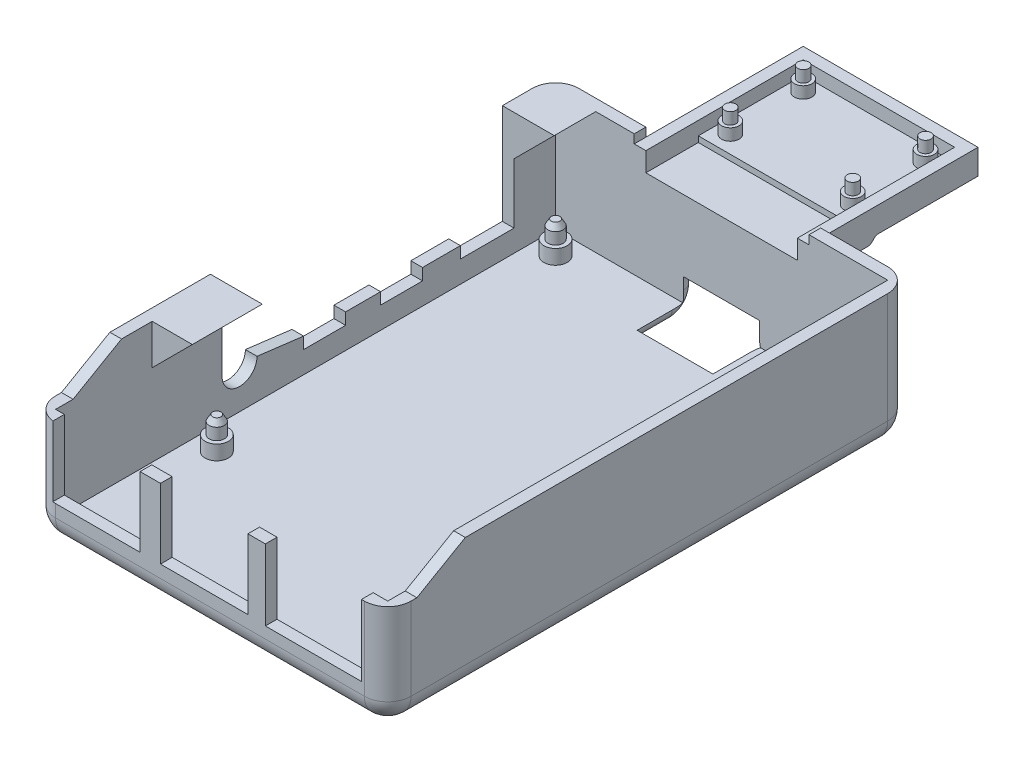
SolidWorks part; units mm, degrees
ref_plane "Płaszczyzna przednia" through (0, 0, 0) normal (0, 0, 1) x (1, 0, 0)
ref_plane "Płaszczyzna górna" through (0, 0, 0) normal (0, 1, 0) x (1, 0, 0)
ref_plane "Płaszczyzna prawa" through (0, 0, 0) normal (1, 0, 0) x (0, 0, -1)
sketch "Szkic1" plane through (0, 0, 0) normal (0, 1, 0) x (1, 0, 0)
  line L1 (-30.5, 44.9) -> (30.5, 44.9)
  line L2 (-30.5, 44.9) -> (-30.5, -44.9)
  line L3 (-30.5, -44.9) -> (30.5, -44.9)
  line L4 (30.5, 44.9) -> (30.5, -44.9)
  line L5 (-30.5, 44.9) -> (30.5, -44.9) construction
  line L6 (-30.5, -44.9) -> (30.5, 44.9) construction
  point P0 (0, 0)
  dimension "D1" = 61
  dimension "D2" = 89.8
extrude "Dodanie-wyciągnięcie1" add sketch "Szkic1" along normal blind 2
sketch "Szkic2" plane through (0, 2, 0) normal (0, 1, 0) x (1, 0, 0)
  line L0 (28.5, -42.9) -> (28.5, 42.9)
  line L1 (28.5, 42.9) -> (-28.5, 42.9)
  line L2 (-28.5, 42.9) -> (-28.5, -42.9)
  line L3 (-28.5, -42.9) -> (28.5, -42.9)
  line L4 (30.5, -44.9) -> (30.5, 44.9)
  line L5 (30.5, 44.9) -> (-30.5, 44.9)
  line L6 (-30.5, 44.9) -> (-30.5, -44.9)
  line L7 (-30.5, -44.9) -> (30.5, -44.9)
  line L8 (30.5, -44.9) -> (30.5, 44.9)
  line L9 (30.5, 44.9) -> (-30.5, 44.9)
  line L10 (-30.5, 44.9) -> (-30.5, -44.9)
  line L11 (-30.5, -44.9) -> (30.5, -44.9)
  dimension "D1" = 0
  dimension "D2" = 2
extrude "Dodanie-wyciągnięcie2" add sketch "Szkic2" along normal blind 16.15
sketch "Szkic3" plane through (0, 0, 44.9) normal (0, 0, 1) x (1, 0, 0)
  line L0 (-30.5, 18.15) -> (30.5, 18.15) construction
  line L1 (-27, 18.15) -> (-12, 18.15)
  line L2 (-27, 18.15) -> (-27, 6.15)
  line L3 (-27, 6.15) -> (-12, 6.15)
  line L4 (-12, 18.15) -> (-12, 6.15)
  line L5 (-30.5, 18.15) -> (-30.5, 0) construction
  line L6 (-8.5, 18.15) -> (6.5, 18.15)
  line L7 (-8.5, 18.15) -> (-8.5, 6.15)
  line L8 (-8.5, 6.15) -> (6.5, 6.15)
  line L9 (6.5, 18.15) -> (6.5, 6.15)
  line L10 (26, 18.15) -> (9.5, 18.15)
  line L11 (26, 18.15) -> (26, 5.95)
  line L12 (26, 5.95) -> (9.5, 5.95)
  line L13 (9.5, 18.15) -> (9.5, 5.95)
  dimension "D1" = 3.5
  dimension "D2" = 15
  dimension "D3" = 3.5
  dimension "D4" = 16.5
  dimension "D5" = 3
  dimension "D6" = 12
  dimension "D7" = 12.2
extrude "Wytnij-wyciągnięcie1" cut sketch "Szkic3" against normal up to surface (2 mm away) up to face at (0, 10.075, 42.9)
sketch "Szkic4" plane through (0, 0, -44.9) normal (0, 0, -1) x (-1, 0, 0)
  line L0 (-30.5, 0) -> (30.5, 0) construction
  line L1 (-6.5, 0) -> (6.5, 0)
  line L2 (-6.5, 0) -> (-6.5, 5.95)
  line L3 (-6.5, 5.95) -> (6.5, 5.95)
  line L4 (6.5, 0) -> (6.5, 5.95)
  line L5 (-6.5, 5.95) -> (-30.5, 5.95)
  line L7 (-30.5, 18.15) -> (-30.5, 0) construction
  line L8 (6.5, 5.95) -> (30.5, 5.95)
  line L9 (30.5, 18.15) -> (30.5, 0) construction
  dimension "D1" = 13
  dimension "D2" = 5.95
extrude "Wytnij-wyciągnięcie2" cut sketch "Szkic4" against normal blind 10 contours L2 L1 L4 L3
sketch "Szkic6" plane through (-30.5, 0, 0) normal (-1, 0, 0) x (0, 0, 1)
  line L0 (-35.77, 18.15) -> (14.33, 18.15)
  line L1 (-35.77, 18.15) -> (-35.77, 5.75)
  line L2 (-35.77, 5.75) -> (14.33, 5.75)
  line L3 (14.33, 18.15) -> (14.33, 5.75)
  line L4 (-26.57, 5.75) -> (-26.57, 7.75)
  line L5 (-26.57, 7.75) -> (-20.07, 7.75)
  line L6 (-20.07, 7.75) -> (-20.07, 5.75)
  line L7 (-12.87, 5.75) -> (-12.87, 7.75)
  line L8 (-12.87, 7.75) -> (-6.87, 7.75)
  line L9 (-6.87, 7.75) -> (-6.87, 5.75)
  line L10 (0.33, 5.75) -> (0.33, 7.75)
  line L11 (0.33, 7.75) -> (8.33, 8.75)
  line L12 (8.33, 8.75) -> (8.33, 5.75)
  line L13 (-6.87, 7.75) -> (0.33, 7.75) construction
  line L14 (-12.87, 7.75) -> (-20.07, 7.75) construction
  line L15 (-44.9, 18.15) -> (44.9, 18.15) construction
  line L16 (-44.9, 0) -> (44.9, 0) construction
  line L17 (-44.9, 18.15) -> (-44.9, 0) construction
  circle A0 centre (11.33, 8.75) radius 3
  line M7 (44.9, 18.15) -> (-44.9, 18.15)
  dimension "D2" = 6
  dimension "D1" = 50.1
  dimension "D3" = 9.2
  dimension "D4" = 7.2
  dimension "D5" = 6.5
  dimension "D6" = 6
  dimension "D7" = 2
  dimension "D8" = 5.75
  dimension "D9" = 9.13
extrude "Wytnij-wyciągnięcie4" cut sketch "Szkic6" against normal up to surface (2 mm away) contours A0 L3 L1 L2 L4 L5 L6 L7 L8 L9 L10 L11 M7 | A0 region at (-30.5, 12.5758, -12.3031) region at (-30.5, 8.75, 11.33) up to face at (-28.5, 10.075, 0)
sketch "Szkic7" plane through (0, 2, 0) normal (0, 1, 0) x (1, 0, 0)
  line L0 (24.57, 38.97) -> (24.57, -19.17) construction
  line L1 (24.57, -19.17) -> (-24.57, -19.17) construction
  line L2 (-24.57, -19.17) -> (-24.57, 38.97) construction
  line L3 (-24.57, 38.97) -> (24.57, 38.97) construction
  line L4 (0, 38.97) -> (0, -19.17) construction
  line L5 (-24.57, 9.9) -> (24.57, 9.9) construction
  line L7 (28.5, -42.9) -> (28.5, 42.9) construction
  line L8 (28.5, 42.9) -> (6.5, 42.9) construction
  line L9 (-28.5, 42.9) -> (-28.5, -42.9) construction
  line L10 (-28.5, -42.9) -> (28.5, -42.9) construction
  circle A0 centre (24.57, -19.17) radius 2
  circle A1 centre (-24.57, -19.17) radius 2
  circle A2 centre (24.57, 38.97) radius 2
  circle A3 centre (-24.57, 38.97) radius 2
  point P12 (0, 9.9)
  dimension "D1" = 4
  dimension "D2" = 3.93
  dimension "D5" = 23.73
  dimension "D3" = 3.93
  dimension "D4" = 3.93
extrude "Dodanie-wyciągnięcie3" add sketch "Szkic7" along normal blind 2.5
ref_plane "haczyki-przednia" through (0, 0, -9.9) normal (0, 0, 1) x (1, 0, 0)
ref_plane "haczyki-prawa" through (0, 0, 0) normal (-1, 0, 0) x (0, 0, 1)
sketch "Szkic8" plane through (0, 4.5, 0) normal (0, 1, 0) x (1, 0, 0)
  circle A0 centre (-24.57, 38.97) radius 1.3
  dimension "D1" = 2.6
extrude "Dodanie-wyciągnięcie4" add sketch "Szkic8" along normal blind 2
sketch "Szkic9" plane through (0, 6.5, 0) normal (0, 1, 0) x (1, 0, 0)
  circle A1 centre (-24.57, 38.97) radius 1.3
  circle A2 centre (-24.57, 38.97) radius 1.3
  dimension "D1" = 0
extrude "Dodanie-wyciągnięcie5" add sketch "Szkic9" along normal blind 1 draft 30
mirror "Lustro1" about plane through (0, 0, 0) normal (-1, 0, 0) of "Dodanie-wyciągnięcie5", "Dodanie-wyciągnięcie4"
mirror "Lustro2" about plane through (0, 0, -9.9) normal (0, 0, 1) of "Lustro1"
sketch "Szkic11" plane through (0, 18.15, 0) normal (0, 1, 0) x (1, 0, 0)
  line L0 (-28.5, 35.77) -> (-30.5, 35.77)
  line L1 (-30.5, 35.77) -> (-30.5, 44.9)
  line L2 (-30.5, 44.9) -> (-20.5, 44.9)
  line L3 (30.5, 44.9) -> (-30.5, 44.9) construction
  line L4 (-20.5, 44.9) -> (-20.5, 42.9)
  line L5 (28.5, 42.9) -> (-28.5, 42.9) construction
  line L6 (-20.5, 42.9) -> (-28.5, 42.9)
  line L7 (-28.5, 42.9) -> (-28.5, 35.77)
  line L8 (-30.5, -14.33) -> (-28.5, -14.33)
  line L9 (-28.5, -14.33) -> (-28.5, -44.9)
  line L10 (-30.5, -44.9) -> (-27, -44.9) construction
  line L11 (-28.5, -44.9) -> (-30.5, -44.9)
  line L12 (-30.5, -44.9) -> (-30.5, -14.33)
  dimension "D1" = 10
extrude "Dodanie-wyciągnięcie6" add sketch "Szkic11" along normal blind 4.8
sketch "Szkic12" plane through (-30.5, 0, 0) normal (-1, 0, 0) x (0, 0, 1)
  line L5 (44.9, 18.15) -> (39.9, 18.15)
  line L6 (44.9, 22.95) -> (44.9, 0) construction
  line L7 (39.9, 18.15) -> (31.5862, 22.95)
  line L8 (14.33, 22.95) -> (44.9, 22.95) construction
  line L9 (31.5862, 22.95) -> (44.9, 22.95)
  line L10 (44.9, 22.95) -> (44.9, 18.15)
  line L11 (44.9, 18.15) -> (42.9, 18.15) construction
  dimension "D1" = 30
  dimension "D2" = 5
extrude "Wytnij-wyciągnięcie5" cut sketch "Szkic12" against normal up to surface (2 mm away) up to face at (-28.5, 10.469, -3.6595)
sketch "Szkic13" plane through (0, 0, 14.33) normal (0, 0, -1) x (-1, 0, 0)
  line L0 (28.5, 22.95) -> (21.6, 22.95)
  line L1 (21.6, 22.95) -> (28.5, 16.05)
  line L2 (28.5, 22.95) -> (28.5, 8.75) construction
  line L3 (28.5, 16.05) -> (28.5, 22.95)
  dimension "D1" = 45
  dimension "D2" = 6.9
extrude "Dodanie-wyciągnięcie7" add sketch "Szkic13" against normal blind 12
sketch "Szkic14" plane through (0, 0, -35.77) normal (0, 0, 1) x (1, 0, 0)
  line L0 (-21.6, 22.95) -> (-28.5, 22.95)
  line L1 (-28.5, 22.95) -> (-28.5, 16.05)
  line L5 (-21.6, 22.95) -> (-30.5, 22.95)
  line L6 (-28.5, 16.05) -> (-21.6, 22.95)
  line L7 (-28.5, 8.75) -> (-28.5, 16.05)
  line L8 (-30.5, 8.75) -> (-28.5, 8.75)
  line L9 (-30.5, 22.95) -> (-30.5, 8.75)
  line L11 (-28.5, 16.05) -> (-21.6, 22.95)
  dimension "D1" = 0
extrude "Dodanie-wyciągnięcie8" add sketch "Szkic14" against normal up to surface (7.13 mm away) up to face at (-4.1, 10.21, -42.9)
sketch "Szkic15" plane through (-30.5, 0, 0) normal (-1, 0, 0) x (0, 0, 1)
  line L0 (14.33, 22.95) -> (31.5862, 22.95) construction
  line L1 (-39.9, 21.95) -> (-36.77, 21.95)
  line L2 (-39.9, 21.95) -> (-39.9, 17.05)
  line L3 (-39.9, 17.05) -> (-36.77, 17.05)
  line L4 (-36.77, 21.95) -> (-36.77, 17.05)
  line L5 (15.33, 21.95) -> (25.33, 21.95)
  line L6 (15.33, 21.95) -> (15.33, 17.05)
  line L7 (15.33, 17.05) -> (25.33, 17.05)
  line L8 (25.33, 21.95) -> (25.33, 17.05)
  line L9 (-44.9, 22.95) -> (-44.9, 0) construction
  line L10 (14.33, 22.95) -> (14.33, 8.75) construction
  line L11 (26.33, 16.05) -> (14.33, 16.05) construction
  line L12 (26.33, 16.05) -> (26.33, 22.95) construction
  line L15 (-35.77, 22.95) -> (-35.77, 5.75) construction
  dimension "D1" = 1
  dimension "D2" = 1
  dimension "D3" = 1
  dimension "D4" = 1
  dimension "D5" = 1
  dimension "D6" = 5
extrude "Wytnij-wyciągnięcie6" cut sketch "Szkic15" against normal up to surface (7.9 mm away) up to face at (-25.05, 19.5, -39.335)
sketch "Szkic16" plane through (0, 0, -39.9) normal (0, 0, 1) x (1, 0, 0)
  line L0 (-27.5, 17.05) -> (-22.6, 21.95)
  line L1 (-22.6, 21.95) -> (-24.0142, 21.95)
  line L2 (-22.6, 21.95) -> (-30.5, 21.95) construction
  line L3 (-24.0142, 21.95) -> (-28.9142, 17.05)
  line L4 (-27.5, 17.05) -> (-30.5, 17.05) construction
  line L5 (-28.9142, 17.05) -> (-27.5, 17.05)
  dimension "D1" = 1
extrude "Dodanie-wyciągnięcie9" add sketch "Szkic16" along normal up to surface (3.13 mm away) up to face at (-27.775, 19.5, -36.77)
sketch "Szkic17" plane through (0, 0, 25.33) normal (0, 0, -1) x (-1, 0, 0)
  line L0 (27.5, 17.05) -> (28.9142, 17.05)
  line L1 (27.5, 17.05) -> (30.5, 17.05) construction
  line L2 (28.9142, 17.05) -> (24.0142, 21.95)
  line L3 (22.6, 21.95) -> (30.5, 21.95) construction
  line L4 (24.0142, 21.95) -> (22.6, 21.95)
  line L5 (22.6, 21.95) -> (27.5, 17.05)
  dimension "D1" = 1
extrude "Dodanie-wyciągnięcie10" add sketch "Szkic17" along normal up to surface (10 mm away) up to face at (-27.775, 19.5, 15.33)
fillet "Zaokrąglenie1" radius 4 9 edges at (-18.5, 0, -44.9) (18.5, 0, -44.9) (30.5, 0, 0) (0, 0, 44.9) (-30.5, 0, 0) (-30.5, 9.075, 44.9) (30.5, 9.075, 44.9) (30.5, 9.075, -44.9) (-30.5, 11.475, -44.9)
fillet "Zaokrąglenie2" radius 2 8 edges at (-6.5, 4.975, -44.9) (-6.5, 1.1716, -43.7284) (6.5, 4.975, -44.9) (6.5, 1.1716, -43.7284) (0, 5.95, -44.9) (-6.5, 0, -37.9) (6.5, 0, -37.9) (0, 0, -34.9)
sketch "Szkic18" plane through (0, 0, -44.9) normal (0, 0, -1) x (-1, 0, 0)
  line L1 (-26.5, 18.15) -> (20.5, 18.15) construction
  line L3 (-13, 18.15) -> (13, 18.15)
  line L4 (0, 7.95) -> (0, 18.15) construction
  line L5 (-8.5, 7.95) -> (8.5, 7.95) construction
  line L8 (-13, 16.15) -> (13, 16.15)
  line L12 (13, 16.15) -> (13, 18.15)
  line L13 (-13, 16.15) -> (-13, 18.15)
  dimension "D3" = 2
extrude "Dodanie-wyciągnięcie13" add sketch "Szkic18" along normal blind 8
sketch "Szkic20" plane through (13, 0, 0) normal (1, 0, 0) x (0, 0, -1)
  line L0 (52.9, 17.15) -> (69.9, 17.15)
  line L1 (52.9, 18.15) -> (52.9, 16.15) construction
  line L2 (69.9, 17.15) -> (69.9, 19.15)
  line L3 (69.9, 19.15) -> (51.9, 19.15)
  line L4 (51.9, 19.15) -> (51.9, 18.15)
  line L5 (52.9, 18.15) -> (44.9, 18.15) construction
  line L6 (51.9, 18.15) -> (52.9, 18.15)
  line L7 (52.9, 18.15) -> (52.9, 17.15)
  line L8 (44.9, 18.15) -> (44.9, 16.15) construction
  dimension "D1" = 25
extrude "Dodanie-wyciągnięcie14" add sketch "Szkic20" against normal up to surface (26 mm away) up to face at (-13, 17.15, -48.9)
sketch "Szkic21" plane through (0, 19.15, 0) normal (0, 1, 0) x (1, 0, 0)
  line L0 (-10.5, 67.4) -> (-10.5, 54.9) construction
  line L1 (-10.5, 54.9) -> (10.5, 54.9) construction
  line L2 (10.5, 54.9) -> (10.5, 67.4) construction
  line L3 (10.5, 67.4) -> (-10.5, 67.4) construction
  line L4 (0, 54.9) -> (0, 67.4) construction
  line L5 (10.5, 61.15) -> (-10.5, 61.15) construction
  line L6 (0, 67.4) -> (0, 69.9) construction
  line L7 (-13, 69.9) -> (13, 69.9) construction
  line L8 (-12, 67.4) -> (-13, 67.4) construction
  line L9 (-10.5, 68.9) -> (-10.5, 69.9) construction
  line L10 (-13, 51.9) -> (-13, 69.9) construction
  circle A0 centre (10.5, 67.4) radius 1.5
  circle A1 centre (10.5, 54.9) radius 1.5
  circle A2 centre (-10.5, 67.4) radius 1.5
  circle A3 centre (-10.5, 54.9) radius 1.5
  point P16 (0, 61.15)
  dimension "D1" = 3
  dimension "D2" = 21
  dimension "D3" = 12.5
extrude "ROZMIESZCZENIE BOLCOW" add sketch "Szkic21" along normal blind 2
sketch "Szkic22" plane through (0, 21.15, 0) normal (0, 1, 0) x (1, 0, 0)
  circle A0 centre (-10.5, 67.4) radius 0.95
  dimension "D1" = 1.9
extrude "Dodanie-wyciągnięcie16" add sketch "Szkic22" along normal blind 2
ref_plane "cam przednia" through (0, 0, -61.15) normal (0, 0, -1) x (-1, 0, 0)
ref_plane "cam prawa" through (0, 0, 0) normal (1, 0, 0) x (0, 0, -1)
mirror "Lustro3" about plane through (0, 0, 0) normal (1, 0, 0) of "Dodanie-wyciągnięcie16"
mirror "Lustro4" about plane through (0, 0, -61.15) normal (0, 0, -1) of "Lustro3"
sketch "Szkic24" plane through (-13, 0, 0) normal (-1, 0, 0) x (0, 0, 1)
  line L8 (-44.9, 18.15) -> (-51.9, 18.15)
  line L9 (-51.9, 18.15) -> (-51.9, 19.15)
  line L10 (-51.9, 19.15) -> (-69.9, 19.15)
  line L11 (-69.9, 19.15) -> (-69.9, 17.15)
  line L12 (-69.9, 17.15) -> (-52.9, 17.15)
  line L13 (-52.9, 17.15) -> (-52.9, 16.15)
  line L14 (-52.9, 16.15) -> (-44.9, 16.15)
  line L15 (-44.9, 16.15) -> (-44.9, 18.15)
  line L16 (-44.9, 18.15) -> (-51.9, 18.15)
  line L17 (-51.9, 18.15) -> (-51.9, 19.15)
  line L18 (-51.9, 19.15) -> (-69.9, 19.15)
  line L19 (-69.9, 19.15) -> (-69.9, 17.15)
  line L20 (-69.9, 17.15) -> (-52.9, 17.15)
  line L21 (-52.9, 17.15) -> (-52.9, 16.15)
  line L22 (-52.9, 16.15) -> (-44.9, 16.15)
  line L23 (-44.9, 16.15) -> (-44.9, 18.15)
  dimension "D1" = 0
extrude "Dodanie-wyciągnięcie17" add sketch "Szkic24" along normal blind 2
sketch "Szkic23" plane through (0, 0, 0) normal (1, 0, 0) x (0, 0, -1)
  line L0 (47.4106, 14.8121) -> (36.0233, 14.8121)
  line L1 (36.0233, 14.8121) -> (36.0233, 25.4669)
  line L2 (36.0233, 25.4669) -> (-50.5468, 25.4669)
  line L3 (-50.5468, 25.4669) -> (-50.5468, -1.836)
  line L4 (-50.5468, -1.836) -> (47.4106, -1.836)
  line L5 (47.4106, -1.836) -> (47.4106, 14.8121)
extrude "assassins" [suppressed] cut sketch "Szkic23" against normal through all and the other way through all
mirror "Lustro5" about plane through (0, 0, 0) normal (1, 0, 0) of "Dodanie-wyciągnięcie17"
sketch "Szkic25" plane through (0, 0, -69.9) normal (0, 0, -1) x (-1, 0, 0)
  line L4 (-15, 17.15) -> (15, 17.15)
  line L5 (15, 17.15) -> (15, 19.15)
  line L6 (15, 19.15) -> (-15, 19.15)
  line L7 (-15, 19.15) -> (-15, 17.15)
  line L8 (-15, 17.15) -> (15, 17.15)
  line L9 (15, 17.15) -> (15, 19.15)
  line L10 (15, 19.15) -> (-15, 19.15)
  line L11 (-15, 19.15) -> (-15, 17.15)
  dimension "D1" = 0
extrude "Dodanie-wyciągnięcie18" add sketch "Szkic25" along normal blind 2
sketch "Szkic26" plane through (0, 19.15, 0) normal (0, 1, 0) x (1, 0, 0)
  line L0 (15, 51.9) -> (15, 44.9)
  line L4 (15, 51.9) -> (15, 71.9)
  line L5 (15, 71.9) -> (-15, 71.9)
  line L6 (-15, 71.9) -> (-15, 51.9)
  line L7 (-15, 51.9) -> (15, 51.9)
  line L8 (15, 51.9) -> (15, 71.9)
  line L9 (15, 71.9) -> (-15, 71.9)
  line L10 (-15, 71.9) -> (-15, 51.9)
  line L11 (-15, 51.9) -> (15, 51.9) construction
  line L13 (-15, 44.9) -> (-15, 51.9)
  line L14 (15, 44.9) -> (15, 42.9)
  line L15 (28.5, 42.9) -> (-20.5, 42.9) construction
  line L16 (15, 42.9) -> (13, 42.9)
  line L17 (13, 42.9) -> (13, 69.9)
  line L18 (13, 69.9) -> (-13, 69.9)
  line L19 (-13, 69.9) -> (-13, 42.9)
  line L20 (-13, 42.9) -> (-15, 42.9)
  line L21 (-15, 42.9) -> (-15, 44.9)
  line L22 (0, 71.9) -> (0, 69.9) construction
  dimension "D2" = 2
  dimension "D1" = 0
extrude "Dodanie-wyciągnięcie19" add sketch "Szkic26" along normal up to surface and the other way up to surface up to face at (-24.6469, 22.95, -41.2669) other way up to face at (-28.7917, 18.15, 42.005)
sketch "Szkic27" plane through (-20.5, 0, 0) normal (1, 0, 0) x (0, 0, -1)
  line L4 (42.9, 18.15) -> (44.9, 18.15)
  line L5 (44.9, 18.15) -> (44.9, 22.95)
  line L6 (44.9, 22.95) -> (42.9, 22.95)
  line L7 (42.9, 22.95) -> (42.9, 18.15)
  line L8 (42.9, 18.15) -> (44.9, 18.15)
  line L9 (44.9, 18.15) -> (44.9, 22.95)
  line L10 (44.9, 22.95) -> (42.9, 22.95)
  line L11 (42.9, 22.95) -> (42.9, 18.15)
  dimension "D1" = 0
extrude "Dodanie-wyciągnięcie20" add sketch "Szkic27" along normal up to surface (5.5 mm away)
sketch "Szkic28" plane through (-15, 0, 0) normal (-1, 0, 0) x (0, 0, 1)
  line L0 (-52.9, 16.15) -> (-48.9, 16.15) construction
  line L2 (-54.9, 17.15) -> (-58.5451, 17.15)
  line L3 (-71.9, 17.15) -> (-52.9, 17.15) construction
  line L4 (-54.9, 17.15) -> (-52.9, 17.15)
  line L5 (-52.9, 17.15) -> (-52.9, 16.15)
  line L6 (-52.9, 16.15) -> (-44.9, 16.15) construction
  arc A0 (-52.9, 16.15) -> (-53.9, 16.65) centre (-52.9, 17.4) cw
  arc A1 (-53.9, 16.65) -> (-54.9, 17.15) centre (-54.9, 15.9) ccw
  line M10 (-71.9, 17.15) -> (-52.9, 17.15)
  line M11 (-52.9, 17.15) -> (-52.9, 16.15)
  dimension "D1" = 2
extrude "Dodanie-wyciągnięcie21" add sketch "Szkic28" against normal up to surface (30 mm away) contours A1 A0 M11 M10 region at (-15, 16.7575, -53.4719)
sketch "Szkic29" plane through (0, 22.95, 0) normal (0, 1, 0) x (1, 0, 0)
  line L0 (-15, 44.9) -> (-15, 42.9)
  line L12 (-15, 44.9) -> (-26.5, 44.9)
  line L13 (-30.5, 40.9) -> (-30.5, 35.77)
  line L14 (-30.5, 35.77) -> (-21.6, 35.77)
  line L15 (-21.6, 35.77) -> (-21.6, 42.9)
  line L16 (-21.6, 42.9) -> (-13, 42.9)
  line L17 (-13, 42.9) -> (-13, 69.9)
  line L18 (-13, 69.9) -> (13, 69.9)
  line L19 (13, 69.9) -> (13, 42.9)
  line L20 (13, 42.9) -> (15, 42.9)
  line L21 (15, 42.9) -> (15, 71.9)
  line L22 (15, 71.9) -> (-15, 71.9)
  line L23 (-15, 71.9) -> (-15, 44.9)
  line L24 (-15, 44.9) -> (-26.5, 44.9)
  line L25 (-30.5, 40.9) -> (-30.5, 35.77)
  line L26 (-30.5, 35.77) -> (-21.6, 35.77)
  line L27 (-21.6, 35.77) -> (-21.6, 42.9)
  line L28 (-21.6, 42.9) -> (-13, 42.9)
  line L29 (-13, 42.9) -> (-13, 69.9)
  line L30 (-13, 69.9) -> (13, 69.9)
  line L31 (13, 69.9) -> (13, 42.9)
  line L32 (13, 42.9) -> (15, 42.9)
  line L33 (15, 42.9) -> (15, 71.9)
  line L34 (15, 71.9) -> (-15, 71.9)
  line L35 (-15, 71.9) -> (-15, 44.9)
  arc A1 (-26.5, 44.9) -> (-30.5, 40.9) centre (-26.5, 40.9) ccw
  arc A2 (-26.5, 44.9) -> (-30.5, 40.9) centre (-26.5, 40.9) ccw
  line M19 (-21.6, 42.9) -> (-13, 42.9)
  line M20 (-13, 42.9) -> (-13, 69.9)
  line M21 (-13, 69.9) -> (13, 69.9)
  line M22 (13, 69.9) -> (13, 42.9)
  line M23 (13, 42.9) -> (15, 42.9)
  line M24 (15, 42.9) -> (15, 71.9)
  line M25 (15, 71.9) -> (-15, 71.9)
  line M26 (-15, 71.9) -> (-15, 44.9)
  dimension "D1" = 0
extrude "Wytnij-wyciągnięcie7" cut sketch "Szkic29" against normal blind 1.5 contours L0 M26 M19 M20 M21 M22 M23 M24 M25 region at (-14.5827, 22.95, -58.4)
sketch "Szkic30" plane through (0, 18.15, 0) normal (0, 1, 0) x (1, 0, 0)
  line L0 (30.5, -31.5862) -> (28.5, -31.5862)
  line L1 (-28.5, -31.5862) -> (-30.5, -31.5862) construction
  line L8 (26.5, 44.9) -> (15, 44.9)
  line L9 (15, 44.9) -> (15, 42.9)
  line L10 (15, 42.9) -> (28.5, 42.9)
  line L11 (28.5, 42.9) -> (28.5, -42.9)
  line L12 (28.5, -42.9) -> (26, -42.9)
  line L13 (26, -42.9) -> (26, -44.9)
  line L14 (26, -44.9) -> (26.5, -44.9)
  line L15 (30.5, -40.9) -> (30.5, 40.9)
  line L16 (26.5, 44.9) -> (15, 44.9)
  line L17 (15, 44.9) -> (15, 42.9)
  line L18 (15, 42.9) -> (28.5, 42.9)
  line L19 (28.5, 42.9) -> (28.5, -42.9)
  line L20 (28.5, -42.9) -> (26, -42.9)
  line L21 (26, -42.9) -> (26, -44.9)
  line L22 (26, -44.9) -> (26.5, -44.9)
  line L23 (30.5, -40.9) -> (30.5, 40.9)
  arc A2 (26.5, -44.9) -> (30.5, -40.9) centre (26.5, -40.9) ccw
  arc A3 (30.5, 40.9) -> (26.5, 44.9) centre (26.5, 40.9) ccw
  arc A4 (26.5, -44.9) -> (30.5, -40.9) centre (26.5, -40.9) ccw
  arc A5 (30.5, 40.9) -> (26.5, 44.9) centre (26.5, 40.9) ccw
  line M12 (26.5, 44.9) -> (15, 44.9)
  line M13 (15, 44.9) -> (15, 42.9)
  line M14 (15, 42.9) -> (28.5, 42.9)
  line M15 (28.5, 42.9) -> (28.5, -42.9)
  line M20 (30.5, -40.9) -> (30.5, 40.9)
  arc M21 (30.5, 40.9) -> (26.5, 44.9) centre (26.5, 40.9) ccw
  dimension "D1" = 0
extrude "Dodanie-wyciągnięcie23" add sketch "Szkic30" along normal up to surface (4.8 mm away) contours L0 M20 M21 M12 M13 M14 M15 region at (29.5, 18.15, 30.8057) up to face at (-26.8667, 22.95, 24.0821)
sketch "Szkic31" plane through (30.5, 0, 0) normal (1, 0, 0) x (0, 0, -1)
  line L0 (-39.9, 18.15) -> (-31.5862, 18.15)
  line L1 (-31.5862, 18.15) -> (-31.5862, 22.95)
  line L22 (42.9, 16.05) -> (35.77, 16.05)
  line L23 (35.77, 16.05) -> (35.77, 5.75)
  line L24 (35.77, 5.75) -> (26.57, 5.75)
  line L25 (26.57, 5.75) -> (26.57, 7.75)
  line L26 (26.57, 7.75) -> (20.07, 7.75)
  line L27 (20.07, 7.75) -> (20.07, 5.75)
  line L28 (20.07, 5.75) -> (12.87, 5.75)
  line L29 (12.87, 5.75) -> (12.87, 7.75)
  line L30 (12.87, 7.75) -> (6.87, 7.75)
  line L31 (6.87, 7.75) -> (6.87, 5.75)
  line L32 (6.87, 5.75) -> (-0.33, 5.75)
  line L33 (-0.33, 5.75) -> (-0.33, 7.75)
  line L34 (-0.33, 7.75) -> (-8.33, 8.75)
  line L35 (-14.33, 8.75) -> (-14.33, 16.05)
  line L36 (-14.33, 16.05) -> (-26.33, 16.05)
  line L37 (-26.33, 16.05) -> (-26.33, 22.95)
  line L38 (-26.33, 22.95) -> (-31.5862, 22.95)
  line L39 (-31.5862, 22.95) -> (-39.9, 18.15)
  line L40 (-39.9, 18.15) -> (-42.9, 18.15)
  line L41 (-42.9, 18.15) -> (-42.9, 2)
  line L42 (-42.9, 2) -> (42.9, 2)
  line L43 (42.9, 2) -> (42.9, 16.05)
  line L44 (42.9, 16.05) -> (35.77, 16.05)
  line L45 (35.77, 16.05) -> (35.77, 5.75)
  line L46 (35.77, 5.75) -> (26.57, 5.75)
  line L47 (26.57, 5.75) -> (26.57, 7.75)
  line L48 (26.57, 7.75) -> (20.07, 7.75)
  line L49 (20.07, 7.75) -> (20.07, 5.75)
  line L50 (20.07, 5.75) -> (12.87, 5.75)
  line L51 (12.87, 5.75) -> (12.87, 7.75)
  line L52 (12.87, 7.75) -> (6.87, 7.75)
  line L53 (6.87, 7.75) -> (6.87, 5.75)
  line L54 (6.87, 5.75) -> (-0.33, 5.75)
  line L55 (-0.33, 5.75) -> (-0.33, 7.75)
  line L56 (-0.33, 7.75) -> (-8.33, 8.75)
  line L57 (-14.33, 8.75) -> (-14.33, 16.05)
  line L58 (-14.33, 16.05) -> (-26.33, 16.05)
  line L59 (-26.33, 16.05) -> (-26.33, 22.95)
  line L60 (-26.33, 22.95) -> (-31.5862, 22.95)
  line L61 (-31.5862, 22.95) -> (-39.9, 18.15)
  line L62 (-39.9, 18.15) -> (-42.9, 18.15)
  line L63 (-42.9, 18.15) -> (-42.9, 2)
  line L64 (-42.9, 2) -> (42.9, 2)
  line L65 (42.9, 2) -> (42.9, 16.05)
  arc A1 (-14.33, 8.75) -> (-8.33, 8.75) centre (-11.33, 8.75) ccw
  arc A2 (-14.33, 8.75) -> (-8.33, 8.75) centre (-11.33, 8.75) ccw
  line M24 (-31.5862, 18.15) -> (-40.9, 18.15)
  line M29 (-31.5862, 22.95) -> (-31.5862, 18.15)
  dimension "D1" = 0
extrude "Dodanie-wyciągnięcie24" add sketch "Szkic31" against normal up to surface (2 mm away) contours L61 M29 M24 region at (30.5, 19.75, 34.3574) up to face at (28.5, 14.3667, 10.5287)
